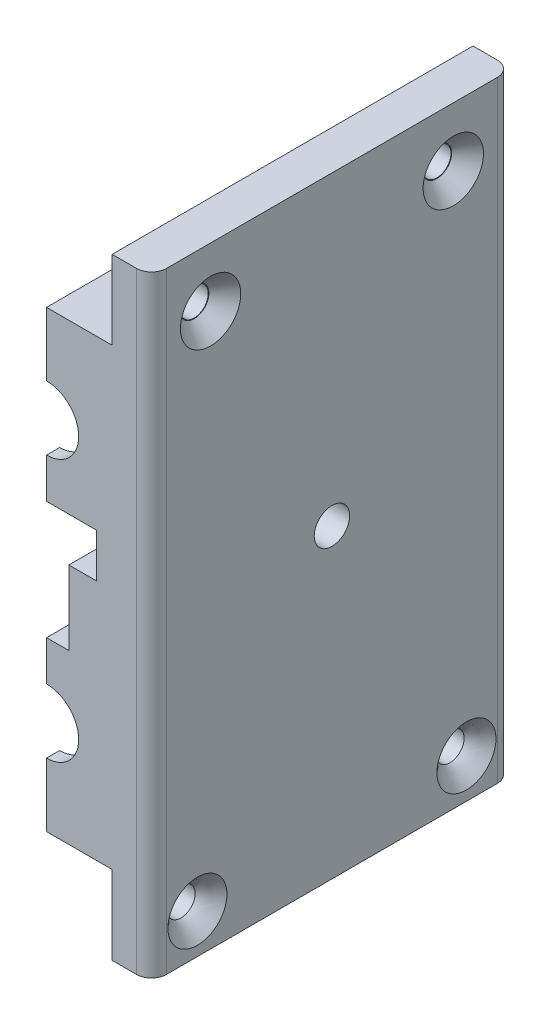
SolidWorks part; units mm, degrees
ref_plane "Front Plane" through (0, 0, 0) normal (0, 0, 1) x (1, 0, 0)
ref_plane "Top Plane" through (0, 0, 0) normal (0, 1, 0) x (1, 0, 0)
ref_plane "Right Plane" through (0, 0, 0) normal (1, 0, 0) x (0, 0, -1)
sketch "Sketch1" plane through (0, 0, 0) normal (0, 0, 1) x (1, 0, 0)
  line L0 (0, 0) -> (0, -93.2)
  line L1 (0, -93.2) -> (-6, -93.2)
  line L2 (-6, -93.2) -> (-6, -81.2)
  line L3 (-6, -81.2) -> (-16, -81.2)
  line L4 (-16, -81.2) -> (-16, -74.2)
  line L5 (-16, -59) -> (-16, -44.3)
  line L6 (-16, -44.3) -> (-8.4, -44.3)
  line L7 (-8.4, -44.3) -> (-8.4, -37.6)
  line L8 (-8.4, -37.6) -> (-16, -37.6)
  line L9 (-16, -37.6) -> (-16, -34.2)
  line L10 (-16, -19) -> (-16, -12)
  line L11 (-16, -12) -> (-6, -12)
  line L12 (-6, -12) -> (-6, 0)
  line L13 (-6, 0) -> (0, 0)
  arc A0 (-16, -74.2) -> (-16, -59) centre (-16, -66.6) ccw
  arc A1 (-16, -34.2) -> (-16, -19) centre (-16, -26.6) ccw
  dimension "D6" = 7.6
  dimension "D7" = 7.6
  dimension "D1" = 6
  dimension "D2" = 12
  dimension "D3" = 12
  dimension "D4" = 14.7
  dimension "D5" = 40
  dimension "D8" = 7
  dimension "D9" = 3.4
  dimension "D11" = 10
  dimension "D12" = 10
extrude "Boss-Extrude1" add sketch "Sketch1" along normal blind 55
ref_plane "Plane1" through (0, 0, 28.5) normal (0, 0, -1) x (-1, 0, 0)
sketch "Sketch2" plane through (0, 0, 28.5) normal (0, 0, -1) x (-1, 0, 0)
  line L0 (16, -34.2) -> (16, -31.5)
  line L1 (16, -21.7) -> (16, -19)
  arc A0 (16, -19) -> (16, -34.2) centre (16, -26.6) ccw
  arc A1 (16, -21.7) -> (16, -31.5) centre (16, -26.6) ccw
  dimension "D1" = 4.9
extrude "Boss-Extrude2" add sketch "Sketch2" along normal blind 2
sketch "Sketch3" plane through (0, 0, 28.5) normal (0, 0, -1) x (-1, 0, 0)
  line L0 (16, -74.2) -> (16, -71.5)
  line L1 (16, -61.7) -> (16, -59)
  arc A0 (16, -59) -> (16, -74.2) centre (16, -66.6) ccw
  arc A1 (16, -61.7) -> (16, -71.5) centre (16, -66.6) ccw
  dimension "D1" = 4.9
extrude "Boss-Extrude3" add sketch "Sketch3" along normal blind 2
ref_plane "Plane2" through (0, 0, 2) normal (0, 0, -1) x (-1, 0, 0)
sketch "Sketch4" plane through (0, 0, 2) normal (0, 0, -1) x (-1, 0, 0)
  line L1 (16, -59) -> (16, -61.7)
  line L2 (16, -74.2) -> (16, -81.2) construction
  line L4 (16, -71.5) -> (16, -74.2)
  line L5 (16, -19) -> (16, -21.7)
  line L6 (16, -31.5) -> (16, -34.2)
  arc A1 (16, -59) -> (16, -74.2) centre (16, -66.6) ccw construction
  arc A2 (16, -74.2) -> (16, -59) centre (16, -66.6) cw
  arc A4 (16, -61.7) -> (16, -71.5) centre (16, -66.6) ccw
  arc A5 (16, -34.2) -> (16, -19) centre (16, -26.6) cw
  arc A6 (16, -21.7) -> (16, -31.5) centre (16, -26.6) ccw
  dimension "D1" = 4.9
  dimension "D2" = 4.9
extrude "Boss-Extrude5" add sketch "Sketch4" along normal blind 2
ref_plane "Plane3" through (0, 0, 53) normal (0, 0, -1) x (-1, 0, 0)
sketch "Sketch5" plane through (0, 0, 53) normal (0, 0, -1) x (-1, 0, 0)
  line L0 (16, -19) -> (16, -21.7)
  line L1 (16, -31.5) -> (16, -34.2)
  line L2 (16, -59) -> (16, -61.7)
  line L3 (16, -71.5) -> (16, -74.2)
  arc A0 (16, -19) -> (16, -34.2) centre (16, -26.6) ccw construction
  arc A1 (16, -34.2) -> (16, -19) centre (16, -26.6) cw
  arc A2 (16, -21.7) -> (16, -31.5) centre (16, -26.6) ccw
  arc A3 (16, -74.2) -> (16, -59) centre (16, -66.6) cw
  arc A4 (16, -61.7) -> (16, -71.5) centre (16, -66.6) ccw
  dimension "D1" = 4.9
extrude "Boss-Extrude6" add sketch "Sketch5" against normal blind 2
sketch "Sketch7" plane through (0, 0, 55) normal (0, 0, 1) x (1, 0, 0)
  line L1 (-16, -44.3) -> (-12.6, -44.3)
  line L2 (-16, -44.3) -> (-16, -55.6)
  line L3 (-16, -55.6) -> (-12.6, -55.6)
  line L4 (-12.6, -44.3) -> (-12.6, -55.6)
  dimension "D1" = 3.4
  dimension "D2" = 11.3
extrude "Cut-Extrude2" cut sketch "Sketch7" against normal up to surface (55 mm away) up to face at (-9.9375, -45.1875, 0)
sketch "Sketch8" plane through (0, 0, 0) normal (1, 0, 0) x (0, 0, -1)
  line L0 (-55, -93.2) -> (-55, 0) construction
  line L1 (0, -93.2) -> (0, 0) construction
  line L2 (-55, 0) -> (0, 0) construction
  line L3 (-55, -93.2) -> (0, -93.2) construction
  circle A0 centre (-46, -9) radius 2.15
  circle A1 centre (-9, -9) radius 2.15
  circle A2 centre (-7, -87.2) radius 2.15
  circle A3 centre (-48, -87.2) radius 2.15
  dimension "D1" = 4.3
  dimension "D2" = 4.3
  dimension "D3" = 4.3
  dimension "D4" = 4.3
  dimension "D5" = 9
  dimension "D6" = 9
  dimension "D7" = 7
  dimension "D8" = 7
  dimension "D9" = 9
  dimension "D10" = 9
  dimension "D11" = 6
  dimension "D12" = 6
extrude "Cut-Extrude3" cut sketch "Sketch8" against normal up to surface (6 mm away) up to face at (-6, -6, 27.5)
sketch "Sketch9" plane through (0, 0, 0) normal (1, 0, 0) x (0, 0, -1)
  line L0 (-55, 0) -> (0, 0) construction
  line L1 (-55, -93.2) -> (-55, 0) construction
  circle A0 centre (-27.5, -46.6) radius 2.7
  dimension "D1" = 5.4
  dimension "D2" = 46.6
  dimension "D3" = 27.5
extrude "Cut-Extrude4" cut sketch "Sketch9" against normal up to surface (12.6 mm away) up to face at (-12.6, -49.95, 27.5)
ref_plane "Plane4" through (-2.5, 0, 0) normal (1, 0, 0) x (0, 0, -1)
sketch "Sketch12" plane through (-2.5, 0, 0) normal (1, 0, 0) x (0, 0, -1)
  circle A1 centre (-46, -9) radius 2.25
  dimension "D1" = 4.5
sketch "Sketch13" plane through (0, 0, 0) normal (1, 0, 0) x (0, 0, -1)
  circle A0 centre (-46, -9) radius 4.6
  dimension "D1" = 9.2
loft "Cut-Loft1" cut profiles "Sketch13", "Sketch12" connector at (0, -9.453, 50.5776) connector at (-2.5, -8.8799, 48.2468)
pattern_linear "LPattern1" count 2 spacing 37 along (0, 0, -1) of "Cut-Loft1"
sketch "Sketch14" plane through (-2.5, 0, 0) normal (1, 0, 0) x (0, 0, -1)
  circle A0 centre (-48, -87.2) radius 2.15 construction
  circle A1 centre (-48, -87.2) radius 2.15
sketch "Sketch15" plane through (0, 0, 0) normal (1, 0, 0) x (0, 0, -1)
  circle A0 centre (-48, -87.2) radius 4.5
  dimension "D1" = 9
loft "Cut-Loft2" cut profiles "Sketch14", "Sketch15" connector at (-2.5, -88.8038, 46.5681) connector at (0, -88.245, 43.623)
pattern_linear "LPattern2" count 2 spacing 41 along (0, 0, -1) of "Cut-Loft2"
fillet "Fillet1" radius 2.3 2 edges at (0, -46.6, 0) (0, -46.6, 55)
